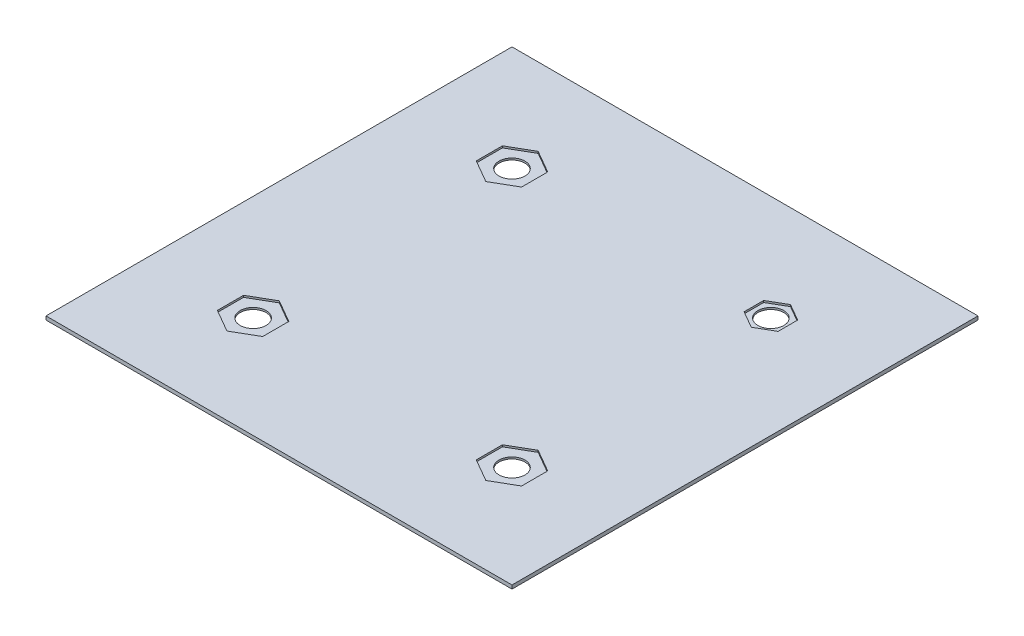
SolidWorks part; units mm, degrees
ref_plane "Front Plane" through (0, 0, 0) normal (0, 0, 1) x (1, 0, 0)
ref_plane "Top Plane" through (0, 0, 0) normal (0, 1, 0) x (1, 0, 0)
ref_plane "Right Plane" through (0, 0, 0) normal (1, 0, 0) x (0, 0, -1)
sketch "Sketch1" plane through (0, 0, 0) normal (0, 1, 0) x (1, 0, 0)
  line L1 (-83.9081, -48.561) -> (30.3919, -48.561)
  line L2 (-83.9081, -48.561) -> (-83.9081, 65.739)
  line L3 (-83.9081, 65.739) -> (30.3919, 65.739)
  line L4 (30.3919, -48.561) -> (30.3919, 65.739)
  dimension "D1" = 114.3
  dimension "D2" = 114.3
extrude "Boss-Extrude1" add sketch "Sketch1" along normal blind 0.889
sketch "Sketch2" plane through (0, 0.889, 0) normal (0, 1, 0) x (1, 0, 0)
  circle A0 centre (-58.5081, 40.339) radius 3.175
  circle A1 centre (4.9919, 40.339) radius 3.175
  circle A2 centre (-58.5081, -23.161) radius 3.175
  circle A3 centre (4.9919, -23.161) radius 3.175
extrude "Cut-Extrude1" cut sketch "Sketch2" against normal blind 10
sketch "Sketch3" plane through (0, 0.889, 0) normal (0, 1, 0) x (1, 0, 0)
  line L1 (-58.5081, 46.7548) -> (-64.0643, 43.5469)
  line L2 (-64.0643, 43.5469) -> (-64.0643, 37.1311)
  line L3 (-64.0643, 37.1311) -> (-58.5081, 33.9232)
  line L4 (-58.5081, 33.9232) -> (-52.9518, 37.1311)
  line L5 (-52.9518, 37.1311) -> (-52.9518, 43.5469)
  line L6 (-52.9518, 43.5469) -> (-58.5081, 46.7548)
  line L7 (4.9919, 45.1509) -> (0.8247, 42.7449)
  line L8 (0.8247, 42.7449) -> (0.8247, 37.9331)
  line L9 (0.8247, 37.9331) -> (4.9919, 35.5272)
  line L10 (4.9919, 35.5272) -> (9.1591, 37.9331)
  line L11 (9.1591, 37.9331) -> (9.1591, 42.7449)
  line L12 (9.1591, 42.7449) -> (4.9919, 45.1509)
  line L13 (-58.5081, -16.7452) -> (-64.0643, -19.9531)
  line L14 (-64.0643, -19.9531) -> (-64.0643, -26.3689)
  line L15 (-64.0643, -26.3689) -> (-58.5081, -29.5768)
  line L16 (-58.5081, -29.5768) -> (-52.9518, -26.3689)
  line L17 (-52.9518, -26.3689) -> (-52.9518, -19.9531)
  line L18 (-52.9518, -19.9531) -> (-58.5081, -16.7452)
  line L19 (4.9919, -16.7452) -> (-0.5643, -19.9531)
  line L20 (-0.5643, -19.9531) -> (-0.5643, -26.3689)
  line L21 (-0.5643, -26.3689) -> (4.9919, -29.5768)
  line L22 (4.9919, -29.5768) -> (10.5482, -26.3689)
  line L23 (10.5482, -26.3689) -> (10.5482, -19.9531)
  line L24 (10.5482, -19.9531) -> (4.9919, -16.7452)
  circle A0 centre (-58.5081, 40.339) radius 5.5563 construction
  circle A1 centre (4.9919, 40.339) radius 4.1672 construction
  circle A2 centre (-58.5081, -23.161) radius 5.5562 construction
  circle A3 centre (4.9919, -23.161) radius 5.5563 construction
extrude "Cut-Extrude2" cut sketch "Sketch3" against normal blind 0.4445
